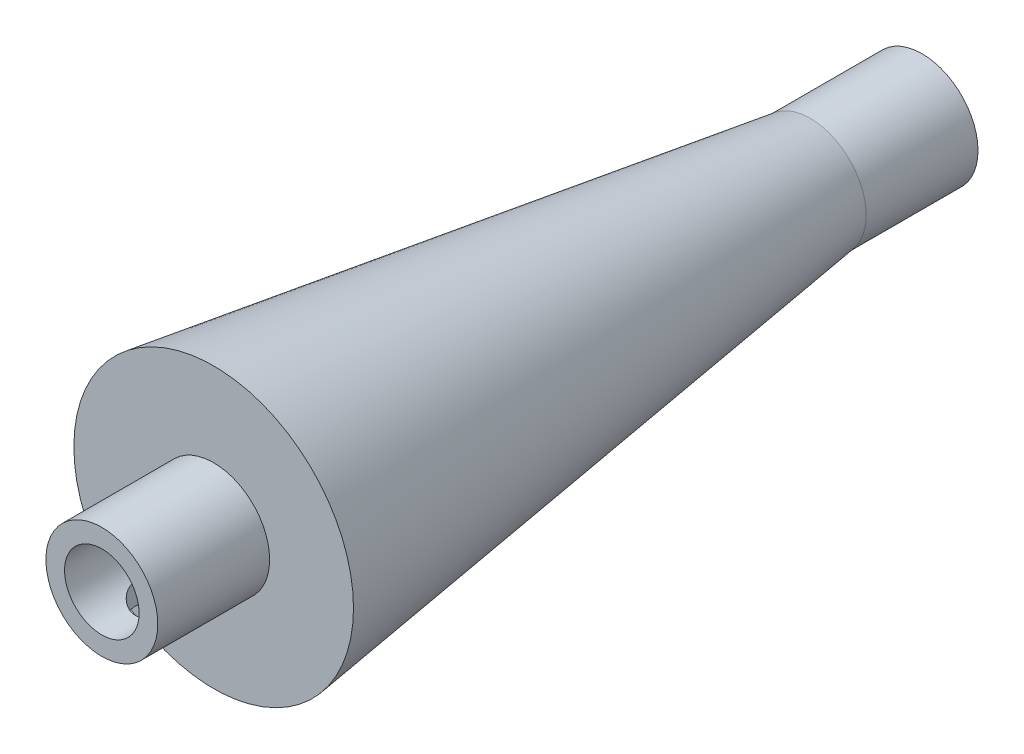
SolidWorks part; units mm, degrees
material "6061-T6 (SS)"
ref_plane "Front Plane" through (0, 0, 0) normal (0, 0, 1) x (1, 0, 0)
ref_plane "Top Plane" through (0, 0, 0) normal (0, 1, 0) x (1, 0, 0)
ref_plane "Right Plane" through (0, 0, 0) normal (1, 0, 0) x (0, 0, -1)
sketch "Sketch1" plane through (0, 0, 0) normal (0, 1, 0) x (1, 0, 0)
  line L0 (4.7625, 23.9683) -> (4.7625, 14.4433) construction
  line L1 (4.7625, 14.4433) -> (-4.7625, 14.4433) construction
  line L2 (11.9063, 23.9683) -> (-11.9062, 23.9683) construction
  line L3 (4.7625, 84.2933) -> (-4.7625, 84.2933) construction
  line L4 (4.7625, 74.7683) -> (4.7625, 84.2933) construction
  line L5 (4.7625, 74.7683) -> (11.9063, 23.9683) construction
  line L7 (4.7625, 23.9683) -> (4.7625, 14.4433)
  line L8 (4.7625, 14.4433) -> (3.175, 14.4433)
  line L9 (11.9063, 23.9683) -> (4.7625, 23.9683)
  line L10 (4.7625, 84.2933) -> (3.175, 84.2933)
  line L11 (4.7625, 74.7683) -> (4.7625, 84.2933)
  line L12 (4.7625, 74.7683) -> (11.9063, 23.9683)
  line L14 (3.175, -1.5875) -> (3.175, 99.7956) construction
  line L15 (3.175, 14.4433) -> (3.175, 84.2933)
  line L16 (0, -1.5875) -> (0, 99.7956) construction
  line L17 (0, -1.5875) -> (0, 99.7956)
revolve "Revolve1" add sketch "Sketch1" angle 360 about L17 region at (5.9394, 0, -44.1131)
ref_plane "Plane1" through (0, -4.7625, 0) normal (0, -1, 0) x (-1, 0, 0)
hole_wizard "#6 Clearance Hole1" positions "Sketch2" profile "Sketch3" hole size "#6" standard "ANSI Inch"
sketch "Sketch2" plane through (0, -4.7625, 0) normal (0, -1, 0) x (-1, 0, 0)
  line L0 (-4.7625, 84.2933) -> (-4.7625, 74.7683) construction
  line L1 (4.7625, 74.7683) -> (4.7625, 84.2933) construction
  line L2 (-4.7625, 84.2933) -> (-4.7625, 74.7683)
  line L3 (4.7625, 74.7683) -> (4.7625, 84.2933)
  line L4 (4.7625, 14.4433) -> (4.7625, 23.9683) construction
  line L5 (-4.7625, 23.9683) -> (-4.7625, 14.4433) construction
  line L6 (4.7625, 14.4433) -> (4.7625, 23.9683)
  line L7 (-4.7625, 23.9683) -> (-4.7625, 14.4433)
  line L8 (4.7625, 19.2058) -> (-4.7625, 19.2058) construction
  line L10 (4.7625, 79.5308) -> (-4.7625, 79.5308) construction
  point P0 (0, 79.5308)
  point P2 (0, 19.2058)
  point P18 (0, 19.2058)
  point P23 (0, 0)
  point P24 (0, 79.5308)
sketch "Sketch3" plane through (0, -4.7625, -79.5308) normal (1, 0, 0) x (0, 0, -1)
  line L0 (0, 0) -> (0, 7.4908)
  line L1 (0, 7.4908) -> (1.8986, 6.35)
  line L2 (1.8986, 6.35) -> (1.8986, 0)
  line L5 (1.8986, 0) -> (0, 0)
  line L10 (0, 7.4908) -> (-1.8987, 6.35) construction
  line L11 (0, -6.35) -> (0, 107.95) construction
  dimension "Hole Dia." = 3.7973
  dimension "Hole Depth" = 6.35
  dimension "Drill Angle" = 118
